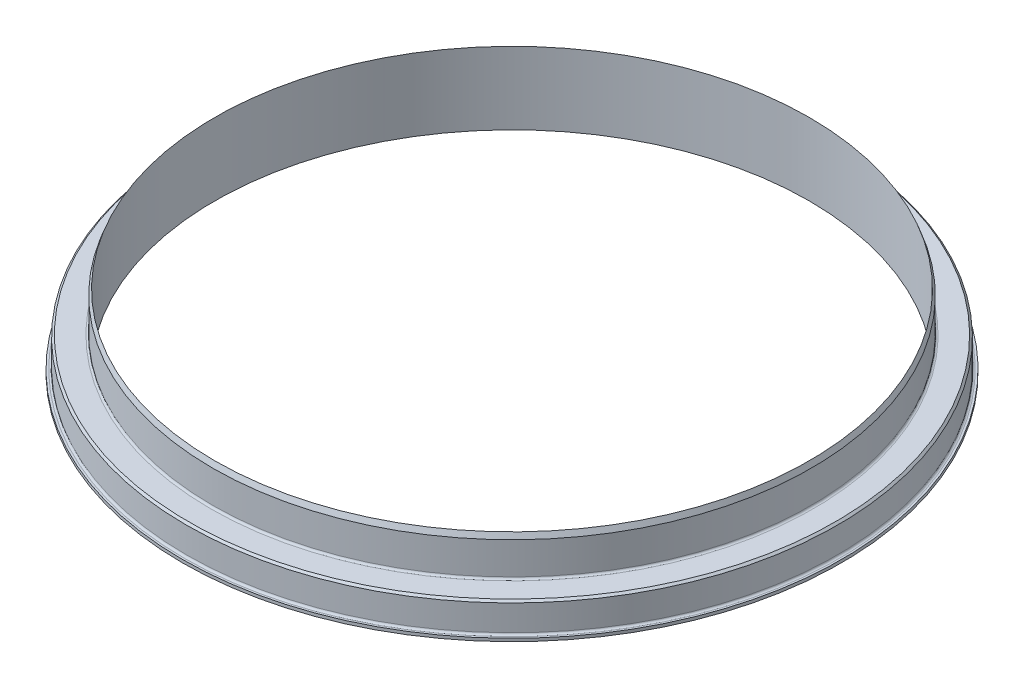
SolidWorks part; units mm, degrees
ref_plane "Front Plane" through (0, 0, 0) normal (0, 0, 1) x (1, 0, 0)
ref_plane "Top Plane" through (0, 0, 0) normal (0, 1, 0) x (1, 0, 0)
ref_plane "Right Plane" through (0, 0, 0) normal (1, 0, 0) x (0, 0, -1)
sketch "Sketch1" plane through (0, 0, 0) normal (0, 0, 1) x (1, 0, 0)
  line L0 (0, 28.739) -> (0, -28.739) construction
  line L1 (0, -55) -> (0, 55) construction
  line L2 (76.2, 28.739) -> (76.2, -28.739) construction
  line L3 (84.455, 28.739) -> (84.455, -28.739) construction
  line L4 (0, 0) -> (84.455, 0) construction
  line L5 (76.2, 18.542) -> (76.2, 0)
  line L6 (76.2, 0) -> (84.455, 0)
  line L7 (83.439, 8.382) -> (83.439, 0.762)
  line L8 (83.439, 8.382) -> (76.708, 8.382)
  line L9 (76.708, 8.382) -> (76.708, 17.1463)
  line L10 (83.439, 0.762) -> (84.455, 0.762)
  line L11 (76.2, 18.542) -> (76.708, 17.1463)
  line L12 (84.455, 0.762) -> (84.455, 0)
  dimension "D1" = 76.2
  dimension "D2" = 84.455
  dimension "D3" = 0.508
  dimension "D5" = 10.16
  dimension "D4" = 6.731
  dimension "D7" = 7.62
  dimension "D8" = 0.762
  dimension "D9" = 1.016
  dimension "D6" = 20
revolve "Revolve1" add sketch "Sketch1" angle 360 about L0
fillet "Fillet1" radius 0.508 2 edges at (0, 8.382, 76.708) (0, 0.762, 83.439)
chamfer "Chamfer1" distance 0.508 angle 45 1 edges at (0, 8.382, 83.439)
equation "\"Di\"= 6.0in"
equation "\"Do\"= 6.65in"
equation "\"Ri\"= \"Di\" / 2"
equation "\"Ro\"= \"Do\" / 2"
equation "\"D1@Sketch1\"=\"Ri\""
equation "\"D2@Sketch1\"=\"Ro\""
